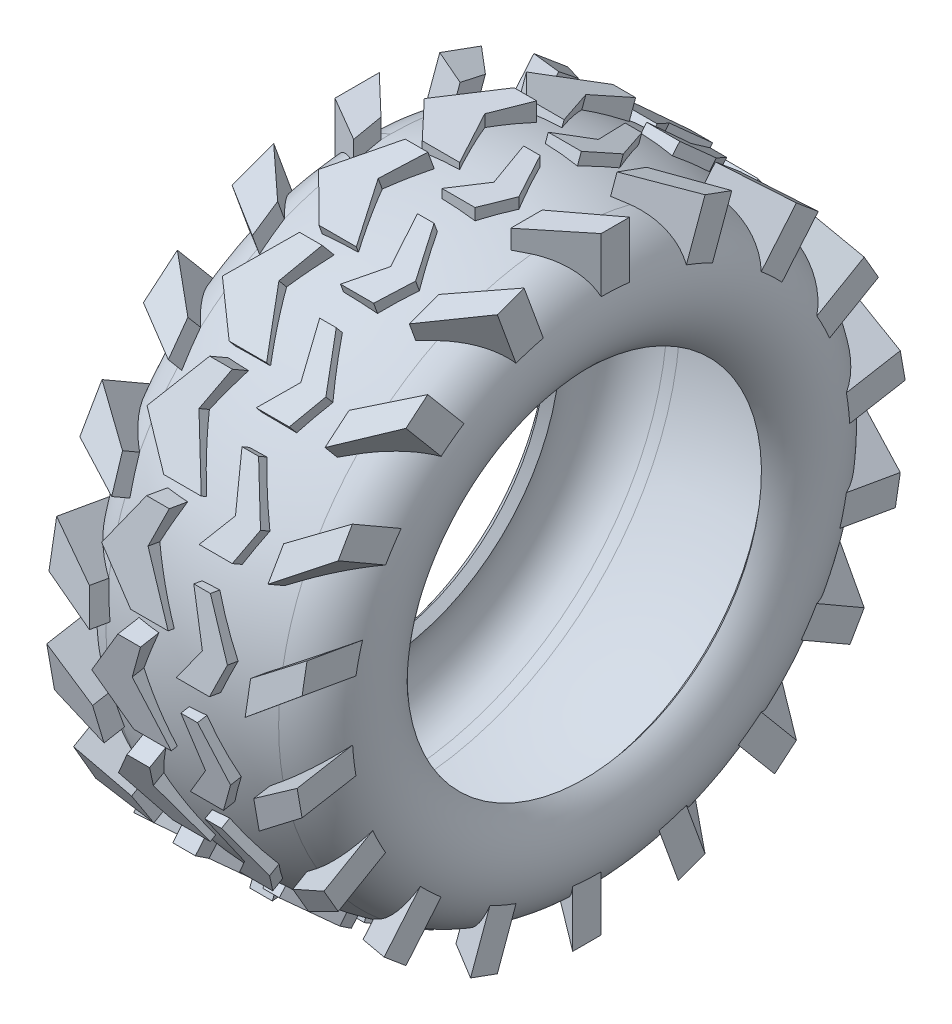
SolidWorks part; units mm, degrees
material "BUTYL"
ref_plane "Front Plane" through (0, 0, 0) normal (0, 0, 1) x (1, 0, 0)
ref_plane "Top Plane" through (0, 0, 0) normal (0, 1, 0) x (1, 0, 0)
ref_plane "Right Plane" through (0, 0, 0) normal (1, 0, 0) x (0, 0, -1)
sketch "Sketch1" plane through (0, 0, 0) normal (0, 0, 1) x (1, 0, 0)
  line L0 (0, 0) -> (-35.7559, 0) construction
  line L2 (0, 88.2362) -> (0, 0) construction
  line L3 (-21.3011, 35) -> (-20, 36.5189)
  line L4 (-14.5291, 54.8089) -> (-14.5291, 54.8089)
  line L5 (-16.4436, 54.2306) -> (-14.5291, 54.8089)
  line L6 (0, 58.8168) -> (0, 56.8168) construction
  line L7 (16.4436, 54.2306) -> (14.5291, 54.8089)
  line L8 (21.3011, 35) -> (20, 36.5189)
  arc A0 (-20, 36.5189) -> (-16.4436, 54.2306) centre (-13.2664, 44.3797) cw
  arc A4 (-21.3011, 35) -> (-17.0576, 56.134) centre (-13.2664, 44.3797) cw
  arc A8 (34, 56.5189) -> (30.4436, 74.2306) centre (27.2664, 64.3797) ccw construction
  arc A9 (35.3011, 55) -> (31.0576, 76.134) centre (27.2664, 64.3797) ccw construction
  arc A10 (30.4436, 74.2306) -> (-73.6302, -86.5981) centre (0, -20.157) ccw construction
  arc A11 (31.0576, 76.134) -> (-75.281, -87.7537) centre (0, -20.157) ccw construction
  arc A12 (-17.0576, 56.134) -> (-75.281, -87.7537) centre (14, -40.157) cw construction
  arc A13 (-16.4436, 54.2306) -> (-73.6302, -86.5981) centre (14, -40.157) cw construction
  arc A14 (-17.0576, 56.134) -> (0, 58.8168) centre (0, 3.2487) cw
  arc A15 (-14.5291, 54.8089) -> (-14.5291, 54.8089) centre (-14.5291, 54.8089) cw
  arc A16 (-14.5291, 54.8089) -> (-14.5291, 54.8089) centre (-14.5291, 54.8089) ccw
  arc A17 (-14.5291, 54.8089) -> (0, 56.8168) centre (0, 3.2487) cw
  arc A18 (14.5291, 54.8089) -> (0, 56.8168) centre (0, 3.2487) ccw
  arc A19 (17.0576, 56.134) -> (0, 58.8168) centre (0, 3.2487) ccw
  arc A20 (21.3011, 35) -> (17.0576, 56.134) centre (13.2664, 44.3797) ccw
  arc A21 (20, 36.5189) -> (16.4436, 54.2306) centre (13.2664, 44.3797) ccw
  dimension "D1" = 20
  dimension "D3" = 35
  dimension "D4" = 2
  dimension "D5" = 58.8168
  dimension "D6" = 21.3011
  dimension "D7" = 14.5291
  dimension "D8" = 16.4436
  dimension "D2" = 2
revolve "Revolve2" add sketch "Sketch1" angle 360 about L0
ref_plane "Plane1" through (0, 60, 0) normal (0, 1, 0) x (1, 0, 0)
sketch "Sketch3" plane through (0, 60, 0) normal (0, 1, 0) x (1, 0, 0)
  line L4 (-24.8187, -3.1425) -> (-24.8187, 5.6216)
  line L5 (14.7839, -8.0063) -> (14.7839, -1.8017)
  line L6 (10.1983, -1.8017) -> (5.2558, 7.3356)
  line L7 (5.2558, 7.3356) -> (1.9776, 7.3356)
  line L8 (1.9776, 7.3356) -> (5.2558, -1.8017)
  line L9 (5.2558, -1.8017) -> (1.1909, -8.0063)
  line L10 (1.1909, -8.0063) -> (7.7271, -8.0063)
  line L11 (7.7271, -8.0063) -> (10.1983, -1.8017)
  line L12 (-1.5119, -1.8017) -> (-7.3575, 9.0052)
  line L13 (-7.3575, 9.0052) -> (-4.4347, 16.3435)
  line L14 (-4.4347, 16.3435) -> (-8.9059, 16.3435)
  line L15 (-8.9059, 16.3435) -> (-15.9304, 5.6216)
  line L16 (-15.9304, 5.6216) -> (-8.9059, -1.8017)
  line L17 (-8.9059, -1.8017) -> (-1.5119, -1.8017)
  line L19 (-17.0576, -56.134) -> (-17.0576, 56.134) construction
  line L21 (-24.8187, 5.6216) -> (-17.0576, -1.8017)
  line L23 (-15.9304, -8.3267) -> (-17.0576, -1.8017)
  line L24 (-15.9304, -8.3267) -> (-24.8187, -3.1425)
  line L25 (14.7839, -8.0063) -> (24.642, 0)
  line L26 (24.642, 0) -> (24.642, 5.6216)
  line L27 (24.642, 5.6216) -> (14.7839, -1.8017)
  dimension "D1" = 7.3941
  dimension "D2" = 10.2201
  dimension "D3" = 12.818
  dimension "D4" = 4.4712
  dimension "D5" = 7.3383
  dimension "D6" = 12.2866
  dimension "D7" = 8.8883
  dimension "D8" = 8.7641
  dimension "D9" = 7.7611
  dimension "D10" = 6.5249
  dimension "D11" = 6.5362
  dimension "D12" = 7.4176
  dimension "D13" = 3.2782
  dimension "D14" = 9.7076
  dimension "D15" = 12.3405
  dimension "D16" = 12.6997
  dimension "D17" = 6.2046
  dimension "D18" = 5.6216
  dimension "D19" = 24.642
  dimension "D20" = 7.5975
  dimension "D21" = 7.3575
  dimension "D22" = 15.9304
  dimension "D23" = 8.9059
  dimension "D24" = 7.5085
  dimension "D25" = 6.7677
  dimension "D26" = 4.5856
  dimension "D27" = 19.3862
  dimension "D28" = 10.7397
extrude "Boss-Extrude1" add sketch "Sketch3" against normal up to next
pattern_circular "CirPattern1" count 18 over 360 about axis through (21.3011, 0, 0) along (1, 0, 0) of "Boss-Extrude1"
